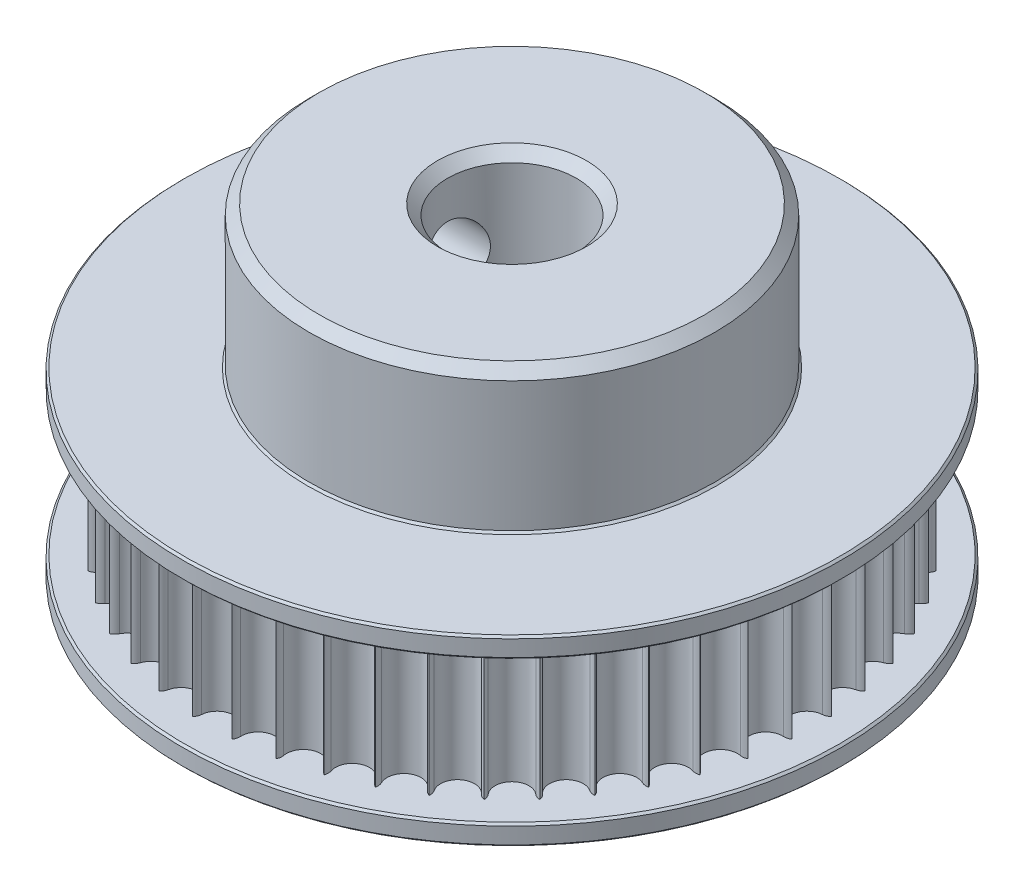
SolidWorks part; units mm, degrees
ref_plane "Front plan" through (0, 0, 0) normal (0, 0, 1) x (1, 0, 0)
ref_plane "Top plan" through (0, 0, 0) normal (0, 1, 0) x (1, 0, 0)
ref_plane "Right plan" through (0, 0, 0) normal (1, 0, 0) x (0, 0, -1)
sketch "Skica2" plane through (0, 0, 0) normal (0, 0, 1) x (1, 0, 0)
  line L0 (10, 8.5) -> (3.175, 8.5)
  line L1 (3.175, 8.5) -> (3.175, -8.5)
  line L2 (3.175, -8.5) -> (4.175, -8.5)
  line L3 (0, -8.5) -> (0, 8.5) construction
  line L4 (0, 8.5) -> (3.175, 8.5)
  line L5 (0, -8.5) -> (3.175, -8.5)
  line L6 (4.175, -8.5) -> (4.175, -7.5)
  line L7 (16.25, 0.5) -> (15, 0.5)
  line L8 (15, 0.5) -> (15, -6.5)
  line L9 (16.25, 0.5) -> (16.25, 1.5)
  line L12 (16.25, -7.5) -> (4.175, -7.5)
  line L13 (16.25, 1.5) -> (10, 1.5)
  line L14 (16.25, -7.5) -> (16.25, -6.5)
  line L15 (15, -6.5) -> (16.25, -6.5)
  line L16 (10, 1.5) -> (10, 8.5)
  point P6 (10.2125, -7.5)
  point P7 (0, 0)
  dimension "D2" = 1
  dimension "D6" = 32.5
  dimension "D3" = 30
  dimension "D1" = 6.35
  dimension "D8" = 17
  dimension "D4" = 1
  dimension "D7" = 20
  dimension "D9" = 7
  dimension "D5" = 1
revolve "Revolute" add sketch "Skica2" angle 360 about L3 region at (8.3994, -0.6081, 0)
sketch "Sketch2" plane through (0, 0.5, 0) normal (0, -1, 0) x (1, 0, 0)
  line L0 (0, 0) -> (0, 14.5385) construction
  line L1 (0, 0) -> (5.0579, 14.1215) construction
  line L3 (0, 0) -> (-2.1506, 14.845) construction
  circle A1 centre (0, 0) radius 13.7025 construction
  circle A2 centre (0, 0) radius 14.5 construction
  arc A3 (-0.8336, 14.476) -> (0.8336, 14.476) centre (0, 14.5385) ccw
  arc A7 (-1.3782, 14.9366) -> (-2.1506, 14.845) centre (0, 0) ccw
  arc A8 (0, 16.4495) -> (2.1506, 14.845) centre (0.5839, 14.9886) cw
  circle A9 centre (0, 0) radius 15 construction
  arc A10 (1.3782, 14.9366) -> (2.1506, 14.845) centre (0, 0) cw
  arc A11 (1.3782, 14.9366) -> (0.8336, 14.476) centre (1.3322, 14.4387) ccw
  arc A12 (0, 16.4495) -> (-2.1506, 14.845) centre (-0.5839, 14.9886) ccw
  arc A13 (-1.3782, 14.9366) -> (-0.8336, 14.476) centre (-1.3322, 14.4387) cw
  dimension "D2" = 1
  dimension "D4" = 0.836
  dimension "D6" = 30
  dimension "D3" = 1.5733
  dimension "D1" = 0.5
extrude "Cut-Extrude3" cut sketch "Sketch2" along normal up to surface (7 mm away) up to face at (16.25, -6.5, 0)
pattern_circular "CirPattern1" count 48 over 360 about axis through (0, -8.5, 0) along (0, -1, 0) of "Cut-Extrude3"
sketch "Sketch3" plane through (0, 0, 0) normal (1, 0, 0) x (0, 0, -1)
  line L0 (0, 8.5) -> (0, 0.5) construction
  line L1 (3.175, 8.5) -> (-3.175, 8.5) construction
  circle A0 centre (0, 4.5) radius 1.65
  dimension "D1" = 3.3
extrude "Cut-Extrude2" cut sketch "Sketch3" against normal up to next
chamfer "Chamfer1" distance 1 angle 45 1 edges at (4.175, -7.5, 0)
chamfer "Chamfer2" distance 0.5 angle 45 2 edges at (10, 8.5, 0) (3.175, 8.5, 0)
chamfer "Chamfer3" distance 0.1 angle 45 5 edges at (16.25, -7.5, 0) (16.25, -6.5, 0) (16.25, 0.5, 0) (16.25, 1.5, 0) (10, 1.5, 0)
equation "\"`\"=2"
equation "\"D6@Sketch2\"= \"D3@Skica2\""
